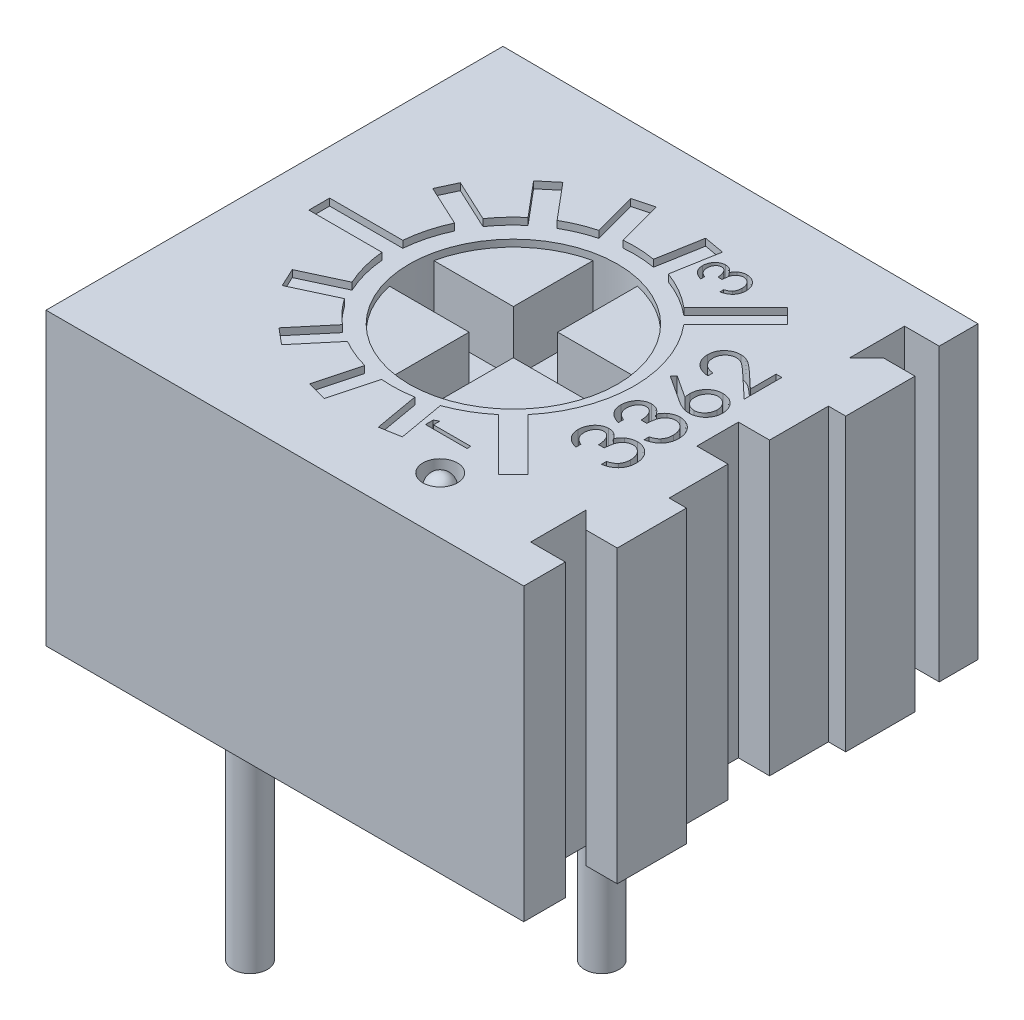
SolidWorks part; units mm, degrees
ref_plane "Front Plane" through (0, 0, 0) normal (0, 0, 1) x (1, 0, 0)
ref_plane "Top Plane" through (0, 0, 0) normal (0, 1, 0) x (1, 0, 0)
ref_plane "Right Plane" through (0, 0, 0) normal (1, 0, 0) x (0, 0, -1)
sketch "Sketch3" plane through (0, 0, 0) normal (0, 1, 0) x (1, 0, 0)
  line L0 (3.1, -1.938) -> (3.55, -1.938)
  line L1 (3.55, -1.938) -> (3.55, -0.938)
  line L2 (3.55, -0.938) -> (3.3, -0.938)
  line L3 (3.3, -0.938) -> (3.3, -0.088)
  line L4 (3.3, -0.088) -> (2.85, -0.088)
  line L5 (2.85, -0.088) -> (2.85, 0.512)
  line L6 (2.85, 0.512) -> (3.3, 0.512)
  line L7 (3.3, 0.512) -> (3.3, 1.362)
  line L8 (3.3, 1.362) -> (3.55, 1.362)
  line L9 (3.55, 1.362) -> (3.55, 2.362)
  line L10 (3.55, 2.362) -> (3.1, 2.362)
  line L11 (3.1, 2.362) -> (2.85, 2.112)
  line L12 (2.85, 2.112) -> (2.85, 2.912)
  line L13 (2.85, 2.912) -> (3.35, 2.912)
  line L14 (3.35, 2.912) -> (3.35, 3.4722)
  line L15 (3.35, 3.4722) -> (-3.55, 3.512)
  line L16 (-3.55, 3.512) -> (-3.55, -3.088)
  line L17 (-3.55, -3.088) -> (3.35, -3.088)
  line L18 (3.35, -3.088) -> (3.35, -2.488)
  line L19 (3.35, -2.488) -> (2.85, -2.488)
  line L20 (2.85, -2.488) -> (2.85, -1.688)
  line L21 (2.85, -1.688) -> (3.1, -1.938)
extrude "Boss-Extrude1" add sketch "Sketch3" along normal blind 4.2
sketch "Sketch5" plane through (0, 4.2, 0) normal (0, 1, 0) x (1, 0, 0)
  line L7 (-0.4351, -2.1839) -> (-0.2602, -1.531)
  line L8 (-0.7249, -2.1063) -> (-0.4351, -2.1839)
  line L9 (-0.5567, -1.4784) -> (-0.7249, -2.1063)
  line L10 (-1.4166, -1.8194) -> (-0.9822, -1.3016)
  line L11 (-1.6464, -1.6266) -> (-1.4166, -1.8194)
  line L12 (-1.2286, -1.1286) -> (-1.6464, -1.6266)
  line L13 (-2.1521, -1.0742) -> (-1.5395, -0.7886)
  line L14 (-2.2789, -0.8023) -> (-2.1521, -1.0742)
  line L15 (-1.6898, -0.5276) -> (-2.2789, -0.8023)
  line L16 (-2.9038, 0.062) -> (-1.8473, 0.062)
  line L17 (-2.9038, 0.362) -> (-2.9038, 0.062)
  line L18 (-1.8473, 0.362) -> (-2.9038, 0.362)
  line L19 (-2.2789, 1.2262) -> (-1.6898, 0.9515)
  line L20 (-2.1521, 1.4981) -> (-2.2789, 1.2262)
  line L21 (-1.5395, 1.2125) -> (-2.1521, 1.4981)
  line L22 (-1.6464, 2.0505) -> (-1.2286, 1.5525)
  line L23 (-1.4166, 2.2433) -> (-1.6464, 2.0505)
  line L24 (-0.9822, 1.7255) -> (-1.4166, 2.2433)
  line L25 (-0.7249, 2.5302) -> (-0.5567, 1.9023)
  line L26 (-0.4351, 2.6078) -> (-0.7249, 2.5302)
  line L27 (-0.2602, 1.9549) -> (-0.4351, 2.6078)
  line L28 (0.313, 2.5755) -> (0.2001, 1.9354)
  line L29 (0.6084, 2.5234) -> (0.313, 2.5755)
  line L30 (0.4911, 1.8578) -> (0.6084, 2.5234)
  line L31 (1.7701, 2.2979) -> (1.0231, 1.5509)
  line L32 (1.9822, 2.0858) -> (1.7701, 2.2979)
  line L33 (1.2352, 1.3388) -> (1.9822, 2.0858)
  line L34 (1.9822, -1.6619) -> (1.2352, -0.9149)
  line L35 (1.7701, -1.874) -> (1.9822, -1.6619)
  line L36 (1.0231, -1.127) -> (1.7701, -1.874)
  line L37 (0.6084, -2.0995) -> (0.4911, -1.4339)
  line L38 (0.313, -2.1516) -> (0.6084, -2.0995)
  line L39 (0.2001, -1.5115) -> (0.313, -2.1516)
  arc A0 (-1.6038, 0.212) -> (1.4038, 0.212) centre (-0.1, 0.212) ccw
  arc A1 (1.4038, 0.212) -> (-1.6038, 0.212) centre (-0.1, 0.212) ccw
  arc A2 (-1.6038, 0.212) -> (1.3962, 0.212) centre (-0.1038, 0.212) ccw
  arc A3 (1.3962, 0.212) -> (-1.6038, 0.212) centre (-0.1038, 0.212) ccw
  arc A4 (-0.9822, -1.3016) -> (-0.5567, -1.4784) centre (-0.1038, 0.212) ccw
  arc A5 (-1.5395, -0.7886) -> (-1.2286, -1.1286) centre (-0.1038, 0.212) ccw
  arc A6 (-1.8473, 0.062) -> (-1.6898, -0.5276) centre (-0.1038, 0.212) ccw
  arc A7 (-1.6898, 0.9515) -> (-1.8473, 0.362) centre (-0.1038, 0.212) ccw
  arc A8 (-1.2286, 1.5525) -> (-1.5395, 1.2125) centre (-0.1038, 0.212) ccw
  arc A9 (-0.5567, 1.9023) -> (-0.9822, 1.7255) centre (-0.1038, 0.212) ccw
  arc A10 (0.2001, 1.9354) -> (-0.2602, 1.9549) centre (-0.1038, 0.212) ccw
  arc A11 (1.0231, 1.5509) -> (0.4911, 1.8578) centre (-0.1038, 0.212) ccw
  arc A12 (1.6462, 0.212) -> (1.2352, 1.3388) centre (-0.1038, 0.212) ccw
  arc A13 (1.2352, -0.9149) -> (1.6462, 0.212) centre (-0.1038, 0.212) ccw
  arc A14 (0.4911, -1.4339) -> (1.0231, -1.127) centre (-0.1038, 0.212) ccw
  arc A15 (-0.2602, -1.531) -> (0.2001, -1.5115) centre (-0.1038, 0.212) ccw
  arc A16 (1.0818, -2.2767) -> (1.5818, -2.2767) centre (1.3318, -2.2767) ccw
  arc A17 (1.5818, -2.2767) -> (1.0818, -2.2767) centre (1.3318, -2.2767) ccw
extrude "Cut-Extrude3" cut sketch "Sketch5" against normal blind 0.2 contours A0 A1
extrude "Cut-Extrude4" cut sketch "Sketch5<5>" against normal blind 0.1 contours L15 L14 L13 A5 L12 L11 L10 A4 L9 L8 L7 A15 L39 L38 L37 A14 L36 L35 L34 A13 A12 L33 L32 L31 A11 L30 L29 L28 A10 L27 L26 L25 A9 L24 L23 L22 A8 L21 L20 L19 A7 L18 L17 L16 A6
sketch "Sketch5<5>" plane through (0, 4.2, 0) normal (0, 1, 0) x (1, 0, 0) same geometry as "Sketch5"
extrude "Cut-Extrude5" cut sketch "Sketch5<6>" against normal blind 0.5 contours A16 A17
sketch "Sketch5<6>" plane through (0, 4.2, 0) normal (0, 1, 0) x (1, 0, 0) same geometry as "Sketch5"
sketch "Sketch9" plane through (0, 4, 0) normal (0, 1, 0) x (1, 0, 0)
  circle A1 centre (-0.1, 0.212) radius 1.5038
  circle A2 centre (-0.1, 0.212) radius 1.5038
  dimension "D1" = 0
sketch "Sketch10" plane through (0, 4.2, 0) normal (0, 1, 0) x (1, 0, 0)
  line L0 (2.6049, 3.4762) -> (2.6049, -3.0878) construction
  line L1 (1.2205, -1.5163) -> (1.2205, -1.9378) construction
  line L2 (1.2491, 1.8945) -> (1.2491, 2.5383) construction
  text T0 "1" font "Century Gothic" height 0.6
  text T1 "3" font "Century Gothic" height 0.6
  text T2 "3362" font "Century Gothic" height 0.8
extrude "Cut-Extrude6" cut sketch "Sketch10" against normal blind 0.3
sketch "Sketch11" plane through (0, 4, 0) normal (0, 1, 0) x (1, 0, 0)
  line L0 (-0.42, 0.532) -> (-0.42, 1.6813)
  line L1 (0.22, 0.532) -> (1.3693, 0.532)
  line L2 (0.22, 0.532) -> (0.22, 1.6813)
  line L3 (-0.42, -1.2574) -> (-0.42, -0.108)
  line L4 (0.22, -1.2574) -> (0.22, -0.108)
  line L5 (-1.5693, -0.108) -> (-0.42, -0.108)
  line L6 (-1.5693, 0.532) -> (-0.42, 0.532)
  line L7 (0.22, -0.108) -> (1.3693, -0.108)
  arc A0 (-1.5693, 0.532) -> (-1.5693, -0.108) centre (-0.1, 0.212) ccw
  circle A1 centre (-0.1, 0.212) radius 1.5038
  arc A2 (-0.42, -1.2574) -> (0.22, -1.2574) centre (-0.1, 0.212) ccw
  arc A3 (0.22, 1.6813) -> (-0.42, 1.6813) centre (-0.1, 0.212) ccw
  arc A4 (1.3693, -0.108) -> (1.3693, 0.532) centre (-0.1, 0.212) ccw
  point P10 (-0.1, 0.212)
  point P18 (-0.1, 0.212)
  dimension "D1" = 0
extrude "Cut-Extrude7" cut sketch "Sketch11" against normal blind 0.89
sketch "Sketch14" plane through (0, 3.7, 0) normal (0, 1, 0) x (1, 0, 0)
  circle A1 centre (1.3318, -2.2767) radius 0.18
extrude "Boss-Extrude2" add sketch "Sketch14" along normal blind 0.32 separate body
sketch "Sketch15" plane through (0, 4.02, 0) normal (0, 1, 0) x (1, 0, 0)
  line L2 (1.2221, -2.4194) -> (1.4415, -2.134)
  circle A1 centre (1.3318, -2.2767) radius 0.18
  arc A2 (1.2221, -2.4194) -> (1.4415, -2.134) centre (1.3318, -2.2767) ccw
  dimension "D1" = 0
revolve "Revolve1" add sketch "Sketch15" angle 180 about L2 reverse direction yes
sketch "Sketch17" plane through (0, 0, 0) normal (0, -1, 0) x (1, 0, 0)
  arc A0 (-1.6443, -2.783) -> (-1.1443, -2.783) centre (-1.3943, -2.783) ccw
  arc A1 (-1.1443, -2.783) -> (-1.6443, -2.783) centre (-1.3943, -2.783) ccw
  arc A2 (0.8957, -0.243) -> (1.3957, -0.243) centre (1.1457, -0.243) ccw
  arc A3 (1.3957, -0.243) -> (0.8957, -0.243) centre (1.1457, -0.243) ccw
  arc A4 (-1.6443, 2.297) -> (-1.1443, 2.297) centre (-1.3943, 2.297) ccw
  arc A5 (-1.1443, 2.297) -> (-1.6443, 2.297) centre (-1.3943, 2.297) ccw
extrude "Boss-Extrude3" add sketch "Sketch17" along normal blind 3.24
